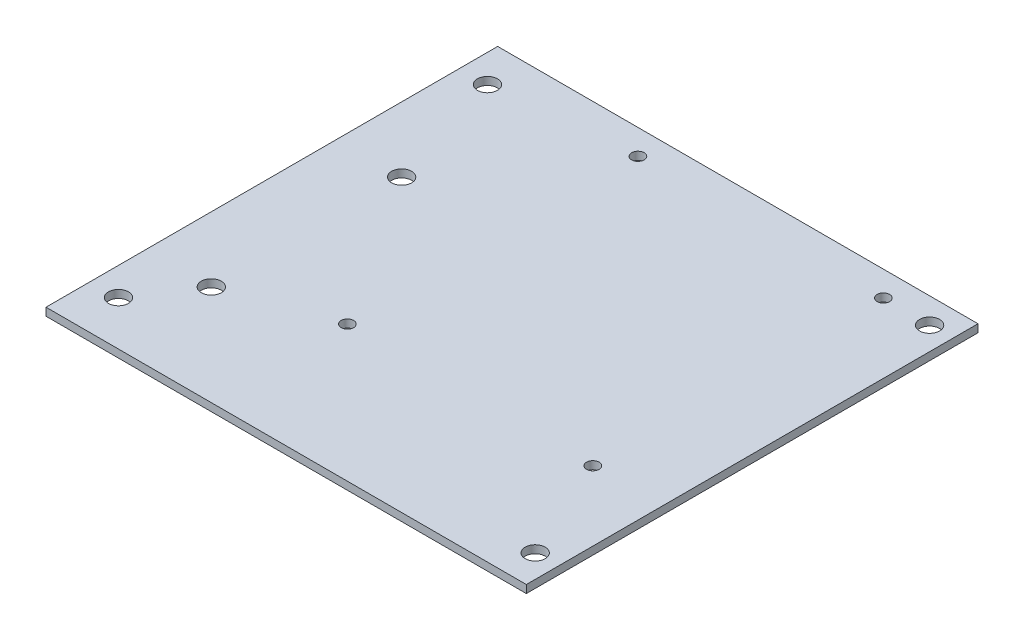
SolidWorks part; units mm, degrees
other "DetailItem3"
material "ABS"
ref_plane "Front Plane" through (0, 0, 0) normal (0, 0, 1) x (1, 0, 0)
ref_plane "Top Plane" through (0, 0, 0) normal (0, 1, 0) x (1, 0, 0)
ref_plane "Right Plane" through (0, 0, 0) normal (1, 0, 0) x (0, 0, -1)
sketch "Sketch1" plane through (0, 0, 0) normal (0, 1, 0) x (1, 0, 0)
  line L1 (-32.2441, 108.719) -> (64.6459, 108.719)
  line L2 (-32.2441, 108.719) -> (-32.2441, 18.549)
  line L3 (-32.2441, 18.549) -> (64.6459, 18.549)
  line L4 (64.6459, 108.719) -> (64.6459, 18.549)
  dimension "D1" = 96.89
  dimension "D2" = 90.17
extrude "PCB" add sketch "Sketch1" along normal blind 1.57
sketch "Sketch2" plane through (0, 1.57, 0) normal (0, 1, 0) x (1, 0, 0)
  line L0 (64.6459, 18.549) -> (64.6459, 108.719) construction
  line L1 (-32.2441, 18.549) -> (64.6459, 18.549) construction
  circle A0 centre (59.5659, 24.899) radius 2
  circle A1 centre (-26.1641, 27.439) radius 2
  circle A2 centre (-26.1641, 101.099) radius 2
  circle A3 centre (59.5659, 103.639) radius 2
  dimension "D3" = 4
  dimension "D6" = 4
  dimension "D11" = 4
  dimension "D12" = 4
  dimension "D1" = 5.08
  dimension "D2" = 6.35
  dimension "D4" = 90.81
  dimension "D5" = 8.89
  dimension "D7" = 90.81
  dimension "D8" = 5.08
  dimension "D9" = 85.09
  dimension "D10" = 82.55
extrude "M3 Mounting Holes" cut sketch "Sketch2" against normal blind 1.57
sketch "Sketch5" plane through (0, 1.57, 0) normal (0, 1, 0) x (1, 0, 0)
  line L0 (64.6459, 108.719) -> (-32.2441, 108.719) construction
  line L1 (-32.2441, 18.549) -> (-31.7441, 18.549)
  line L2 (-32.2441, 18.549) -> (-32.2441, 108.719)
  line L3 (-32.2441, 108.719) -> (-31.7441, 108.719)
  line L4 (-31.7441, 18.549) -> (-31.7441, 108.719)
  line L5 (-32.2441, 18.549) -> (64.6459, 18.549) construction
  line L6 (64.6459, 108.719) -> (64.1459, 108.719)
  line L7 (64.6459, 108.719) -> (64.6459, 18.549)
  line L8 (64.6459, 18.549) -> (64.1459, 18.549)
  line L9 (64.1459, 108.719) -> (64.1459, 18.549)
  dimension "D1" = 0.5
  dimension "D2" = 0.5
extrude "Cut-Extrude1" cut sketch "Sketch5" against normal through all
sketch "Sketch8" plane through (0, 1.57, 0) normal (0, 1, 0) x (1, 0, 0)
  line L1 (-31.7441, 18.549) -> (-31.7441, 108.719) construction
  line L3 (64.1459, 108.719) -> (-31.7441, 108.719) construction
  circle A0 centre (1.2559, 45.719) radius 1.25
  circle A1 centre (50.2559, 45.719) radius 1.25
  circle A2 centre (1.2559, 103.719) radius 1.25
  circle A3 centre (50.2559, 103.719) radius 1.25
  dimension "D1" = 2.5
  dimension "D3" = 2.5
  dimension "D5" = 2.5
  dimension "D6" = 2.5
  dimension "D2" = 5
  dimension "D4" = 63
  dimension "D7" = 58
  dimension "D8" = 58
  dimension "D9" = 49
  dimension "D10" = 33
  dimension "D11" = 33
  dimension "D12" = 49
extrude "RPi mounting hole" cut sketch "Sketch8" against normal blind 10
sketch "Sketch9" plane through (0, 1.57, 0) normal (0, 1, 0) x (1, 0, 0)
  line L0 (-31.7441, 18.549) -> (64.1459, 18.549) construction
  line L1 (-31.7441, 18.549) -> (-31.7441, 108.719) construction
  circle A0 centre (-18.7441, 76.549) radius 2
  circle A1 centre (-18.7441, 38.549) radius 2
  dimension "D1" = 4
  dimension "D2" = 4
  dimension "D3" = 38
  dimension "D4" = 20
  dimension "D5" = 13
  dimension "D6" = 13
extrude "PowerAdapterHoles" cut sketch "Sketch9" against normal blind 10
